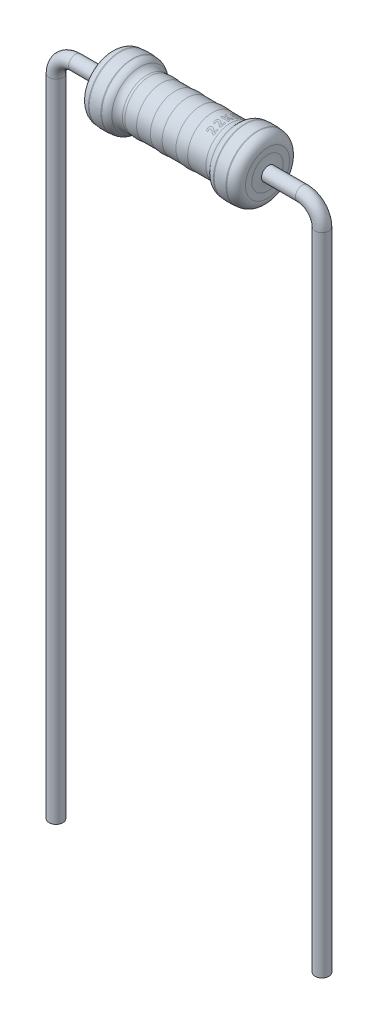
SolidWorks part; units mm, degrees
material "Plain Carbon Steel"
ref_plane "Front Plane" through (0, 0, 0) normal (0, 0, 1) x (1, 0, 0)
ref_plane "Top Plane" through (0, 0, 0) normal (0, 1, 0) x (1, 0, 0)
ref_plane "Right Plane" through (0, 0, 0) normal (1, 0, 0) x (0, 0, -1)
sketch "Sketch1" plane through (0, 0, 0) normal (0, 0, 1) x (1, 0, 0)
  line L0 (-4.33, 0) -> (4.33, 0)
  line L1 (-5.08, -0.75) -> (-5.08, -25.4)
  line L2 (5.08, -0.75) -> (5.08, -25.4)
  line L3 (-5.08, -25.4) -> (5.08, -25.4) construction
  line L4 (0, 0) -> (0, -25.4) construction
  arc A0 (-4.33, 0) -> (-5.08, -0.75) centre (-4.33, -0.75) ccw
  arc A1 (4.33, 0) -> (5.08, -0.75) centre (4.33, -0.75) cw
  dimension "D2" = 0.75
  dimension "D1" = 10.16
  dimension "D3" = 25.4
ref_plane "Plane1" through (-5.08, -25.4, 0) normal (0, -1, 0) x (-1, 0, 0)
sketch "Sketch2" plane through (-5.08, -25.4, 0) normal (0, -1, 0) x (-1, 0, 0)
  circle A0 centre (0, 0) radius 0.265
  dimension "D1" = 0.53
sweep "Sweep1" add profiles "Sketch2" path "Sketch1"
sketch "Sketch3" plane through (0, 0, 0) normal (0, 0, 1) x (1, 0, 0)
  line L0 (-3, 0) -> (3, 0)
  line L5 (-3, 0) -> (-3, 1.2)
  line L6 (3, 0) -> (3, 1.2)
  line L7 (-3, 1.2) -> (-1.8, 1.2)
  line L8 (3, 1.2) -> (1.8, 1.2)
  line L9 (-1.8, 1.2) -> (-1.8, 0.95)
  line L10 (-1.8, 0.95) -> (1.8, 0.95)
  line L11 (1.8, 0.95) -> (1.8, 1.2)
  line L12 (0, 0) -> (0, 0.95) construction
  dimension "D1" = 6
  dimension "D2" = 1.2
  dimension "D3" = 3.6
  dimension "D4" = 0.95
  dimension "D5" = 0.25
revolve "Revolve1" add sketch "Sketch3" angle 360 about L0
fillet "Fillet-1" radius 0.35 2 edges at (1.8, 0, 1.2) (-1.8, 0, 1.2)
fillet "Fillet-2" radius 0.36 4 edges at (3, 0, 1.2) (-3, 0, 1.2) (1.8, 0, 0.95) (-1.8, 0, 0.95)
sketch "Sketch5" plane through (0, 0, 0) normal (0, 0, 1) x (1, 0, 0)
  line L0 (-2.64, -1.2) -> (-2.1354, -1.2) construction
  line L5 (-2.3877, -1.2) -> (-2.3877, 0) construction
  line L10 (-3, 1.2) -> (-1.8, 1.2) construction
  line L15 (-1.05, 0.95) -> (-0.525, 0.95) construction
  line L16 (-3, 0) -> (3, 0) construction
  line L17 (-2.6127, 1.2) -> (-2.1627, 1.2) construction
  line L18 (-2.6127, 1.2) -> (-2.6127, 0) construction
  line L19 (-2.6127, 0) -> (-2.1627, 0) construction
  line L20 (-2.1627, 1.2) -> (-2.1627, 0) construction
  line L21 (-1.8, 0.95) -> (1.8, 0.95) construction
  line L22 (2.6127, 1.2) -> (2.1627, 1.2) construction
  line L23 (2.6127, 1.2) -> (2.6127, 0) construction
  line L24 (2.6127, 0) -> (2.1627, 0) construction
  line L25 (2.1627, 1.2) -> (2.1627, 0) construction
  line L26 (-1.05, 0.95) -> (-1.5, 0.95) construction
  line L27 (-1.05, 0.95) -> (-1.05, 0) construction
  line L28 (-1.05, 0) -> (-1.5, 0) construction
  line L29 (-1.5, 0.95) -> (-1.5, 0) construction
  line L30 (-2.3877, 1.2) -> (-2.3877, 1.22) construction
  line L31 (-0.075, 0.95) -> (-0.525, 0.95) construction
  line L32 (-0.075, 0.95) -> (-0.075, 0) construction
  line L33 (-0.075, 0) -> (-0.525, 0) construction
  line L34 (-0.525, 0.95) -> (-0.525, 0) construction
  line L35 (-1.275, 0.95) -> (-1.275, 0.97) construction
  line L36 (-0.3, 0.95) -> (-0.3, 0.97) construction
  line L37 (2.3877, 1.2) -> (2.3877, 1.22) construction
  line L39 (2.1354, -1.2) -> (2.64, -1.2) construction
  line L41 (2.3877, -1.2) -> (2.3877, 0) construction
  line L44 (3, 1.2) -> (1.8, 1.2) construction
  line L46 (-0.075, 0.95) -> (0.45, 0.95) construction
  line L48 (-3, 0) -> (-3, 0.6)
  line L49 (-3, 0) -> (-3, 1.2) construction
  line L50 (-3, 0) -> (-3.05, 0)
  line L51 (-3.05, 0) -> (-3.05, 0.2)
  line L52 (3, 0) -> (3.05, 0)
  line L53 (3.05, 0) -> (3.05, 0.2)
  line L54 (3, 0) -> (3, 0.6)
  line L55 (3, 0) -> (3, 1.2) construction
  line L56 (-1.05, 0) -> (-0.525, 0) construction
  line L58 (-0.075, 0) -> (0.45, 0) construction
  line L59 (0.45, 0) -> (0.45, 0.95) construction
  line L60 (0.45, 0) -> (0.9, 0) construction
  line L61 (0.9, 0) -> (0.9, 0.95) construction
  line L62 (1.5946, 0.95) -> (-1.5946, 0.95) construction
  line L63 (0.9, 0.95) -> (0.45, 0.95) construction
  line L64 (0.675, 0.95) -> (0.675, 0.97) construction
  arc A0 (-2.6127, 1.2) -> (-2.1627, 1.2) centre (-2.3877, -0.0556) cw construction
  arc A1 (-1.5, 0.95) -> (-1.05, 0.95) centre (-1.275, -0.3056) cw construction
  arc A2 (-0.525, 0.95) -> (-0.075, 0.95) centre (-0.3, -0.3056) cw construction
  arc A3 (2.1627, 1.2) -> (2.6127, 1.2) centre (2.3877, -0.0556) cw construction
  arc A6 (-3, 0.6) -> (-3.05, 0.2) centre (-4.625, 0.6) cw
  arc A7 (3.05, 0.2) -> (3, 0.6) centre (4.625, 0.6) cw
  arc A8 (0.45, 0.95) -> (0.9, 0.95) centre (0.675, -0.3056) cw construction
  dimension "D4" = 0.02
  dimension "D5" = 0.05
  dimension "D7" = 0.6
  dimension "D2" = 1.5
  dimension "D3" = 2.4
  dimension "D1" = 0.45
  dimension "D6" = 0.2
revolve "Revolve Ends" add sketch "Sketch5" angle 360 about L19
sketch "Sketch12" plane through (0, 0, 0) normal (0, 0, 1) x (1, 0, 0)
  line L0 (-2.6127, 0) -> (-2.1627, 0) construction
  line L1 (-2.6127, 0) -> (-2.1627, 0)
  line L2 (-2.6127, 1.2) -> (-2.6127, 0) construction
  line L3 (-2.6127, 1.2) -> (-2.6127, 0)
  line L4 (-2.1627, 1.2) -> (-2.1627, 0) construction
  line L5 (-2.1627, 1.2) -> (-2.1627, 0)
  arc A0 (-2.1627, 1.2) -> (-2.6127, 1.2) centre (-2.3877, -0.0556) ccw construction
  arc A1 (-2.1627, 1.2) -> (-2.6127, 1.2) centre (-2.3877, -0.0556) ccw
revolve "Revolve BAND 1" add sketch "Sketch12" angle 360 about L19
sketch "Sketch7" plane through (0, 0, 0) normal (0, 0, 1) x (1, 0, 0)
  line L0 (-1.05, 0) -> (-1.5, 0) construction
  line L1 (-1.05, 0.95) -> (-1.05, 0) construction
  line L2 (-1.5, 0.95) -> (-1.5, 0) construction
  line L3 (-1.05, 0.95) -> (-1.05, 0)
  line L4 (-1.5, 0.95) -> (-1.5, 0)
  line L5 (-1.05, 0) -> (-1.5, 0)
  arc A0 (-1.05, 0.95) -> (-1.5, 0.95) centre (-1.275, -0.3056) ccw construction
  arc A1 (-1.05, 0.95) -> (-1.5, 0.95) centre (-1.275, -0.3056) ccw
revolve "Revolve BAND 2" add sketch "Sketch7" angle 360 about L28
sketch "Sketch8" plane through (0, 0, 0) normal (0, 0, 1) x (1, 0, 0)
  line L0 (-0.075, 0.95) -> (-0.075, 0) construction
  line L1 (-0.075, 0) -> (-0.525, 0) construction
  line L2 (-0.525, 0.95) -> (-0.525, 0) construction
  line L3 (-0.075, 0.95) -> (-0.075, 0)
  line L4 (-0.075, 0) -> (-0.525, 0)
  line L5 (-0.525, 0.95) -> (-0.525, 0)
  arc A0 (-0.075, 0.95) -> (-0.525, 0.95) centre (-0.3, -0.3056) ccw construction
  arc A1 (-0.075, 0.95) -> (-0.525, 0.95) centre (-0.3, -0.3056) ccw
revolve "Revolve BAND 3" add sketch "Sketch8" angle 360 about L33
sketch "Sketch9" plane through (0, 0, 0) normal (0, 0, 1) x (1, 0, 0)
  line L0 (0.9, 0) -> (0.9, 0.95) construction
  line L1 (0.45, 0) -> (0.45, 0.95) construction
  line L2 (0.45, 0) -> (0.9, 0) construction
  line L3 (0.9, 0) -> (0.9, 0.95)
  line L4 (0.45, 0) -> (0.45, 0.95)
  line L5 (0.45, 0) -> (0.9, 0)
  arc A0 (0.9, 0.95) -> (0.45, 0.95) centre (0.675, -0.3056) ccw construction
  arc A1 (0.9, 0.95) -> (0.45, 0.95) centre (0.675, -0.3056) ccw
revolve "Revolve BAND 4" add sketch "Sketch9" angle 360 about L60
sketch "Sketch11" plane through (0, 0, 0) normal (0, 0, 1) x (1, 0, 0)
  line L0 (2.6127, 1.2) -> (2.6127, 0) construction
  line L1 (2.1627, 1.2) -> (2.1627, 0) construction
  line L2 (2.6127, 0) -> (2.1627, 0) construction
  line L3 (2.6127, 1.2) -> (2.6127, 0)
  line L4 (2.1627, 1.2) -> (2.1627, 0)
  line L5 (2.6127, 0) -> (2.1627, 0)
  arc A0 (2.6127, 1.2) -> (2.1627, 1.2) centre (2.3877, -0.0556) ccw construction
  arc A1 (2.6127, 1.2) -> (2.1627, 1.2) centre (2.3877, -0.0556) ccw
revolve "Revolve5" add sketch "Sketch11" angle 360 about L24
ref_plane "Plane2" through (0, 2, 0) normal (0, 1, 0) x (1, 0, 0)
sketch "Sketch6" plane through (0, 2, 0) normal (0, 1, 0) x (1, 0, 0)
  line L0 (0, 0) -> (1.5, 0) construction
  line L1 (1.5, 1) -> (1.5, -1) construction
  text T0 "22KΩ" font "Calibri" height 0.3
  dimension "D1" = 1.5
  dimension "D2" = 2
wrap "Wrap1" sketch "Sketch6" wrap type scribe source sketch "Sketch6" face at (1.5946, 0, 0.95)
